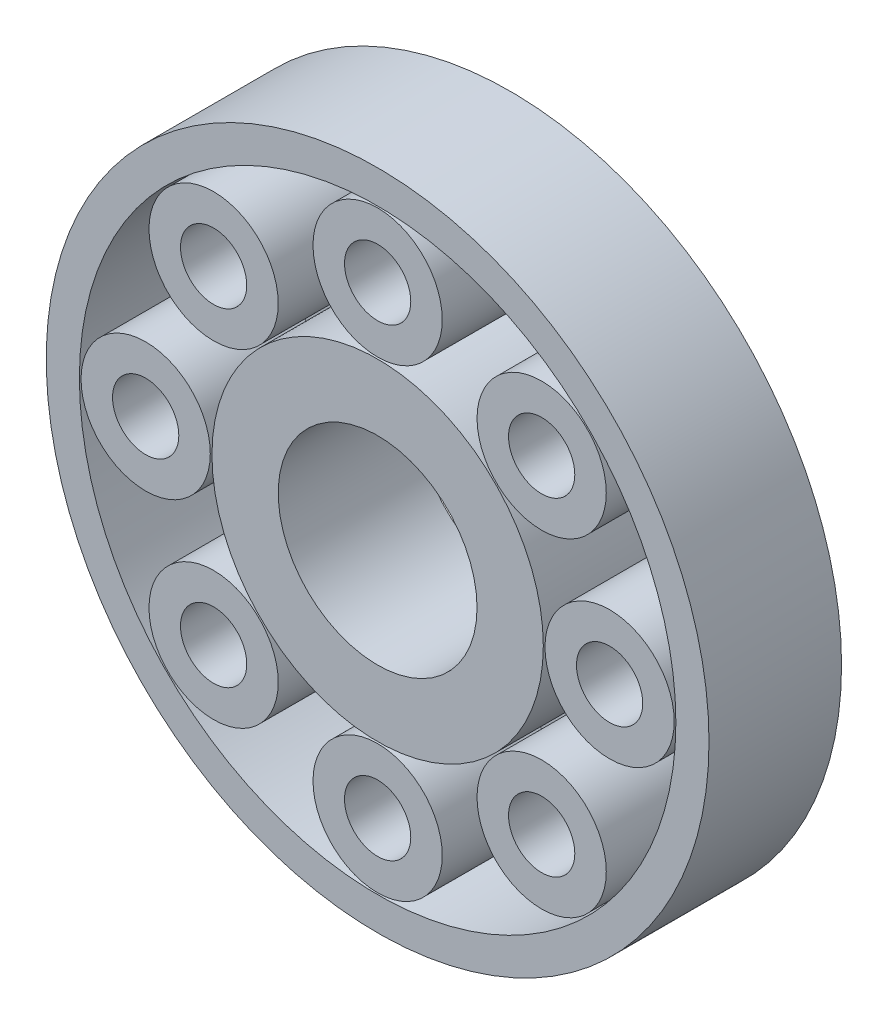
SolidWorks part; units mm, degrees
ref_plane "Front Plane" through (0, 0, 0) normal (0, 0, 1) x (1, 0, 0)
ref_plane "Top Plane" through (0, 0, 0) normal (0, 1, 0) x (1, 0, 0)
ref_plane "Right Plane" through (0, 0, 0) normal (1, 0, 0) x (0, 0, -1)
sketch "Sketch1" plane through (0, 0, 0) normal (0, 0, 1) x (1, 0, 0)
  circle A0 centre (0, 0) radius 10
  dimension "D1" = 20
extrude "Boss-Extrude1" add sketch "Sketch1" along normal blind 4
sketch "Sketch5" plane through (0, 0, 0) normal (0, 0, -1) x (-1, 0, 0)
  circle A0 centre (0, 0) radius 9
  circle A1 centre (0, 0) radius 10 construction
  circle A2 centre (0, 7) radius 1.95
  circle A3 centre (0, 0) radius 5
  circle A4 centre (4.9497, 4.9497) radius 1.95
  circle A5 centre (7, 0) radius 1.95
  circle A6 centre (4.9497, -4.9497) radius 1.95
  circle A7 centre (0, -7) radius 1.95
  circle A8 centre (-4.9497, -4.9497) radius 1.95
  circle A9 centre (-7, 0) radius 1.95
  circle A10 centre (-4.9497, 4.9497) radius 1.95
  point P24 (0, 0)
  dimension "D1" = 1
  dimension "D2" = 3.9
  dimension "D4" = 10
  dimension "D3" = 7
extrude "Cut-Extrude5" cut sketch "Sketch5" against normal up to surface (4 mm away) from offset 0.5 contours A7 A0 A6 A3 | A8 A0 A7 A3 | A9 A0 A8 A3 | A10 A0 A9 A3 | A10 A3 A2 A0 | A4 A0 A2 A3 | A5 A0 A4 A3 | A6 A0 A5 A3 region at (8.9745, 0, 0) up to face at (10, 0, 4) offset against normal yes
sketch "Sketch10" plane through (0, 0, 0) normal (0, 0, -1) x (-1, 0, 0)
  circle A0 centre (0, 0) radius 4
  dimension "D1" = 8
extrude "Boss-Extrude12" add sketch "Sketch10" along normal blind 0.2
sketch "Sketch8" plane through (0, 0, 4) normal (0, 0, 1) x (1, 0, 0)
  circle A0 centre (0, 0) radius 3
  circle A1 centre (0, 7) radius 1
  circle A3 centre (4.9497, 4.9497) radius 1
  circle A4 centre (7, 0) radius 1
  circle A5 centre (4.9497, -4.9497) radius 1
  circle A6 centre (0, -7) radius 1
  circle A7 centre (-4.9497, -4.9497) radius 1
  circle A8 centre (-7, 0) radius 1
  circle A9 centre (-4.9497, 4.9497) radius 1
  circle A10 centre (0, 0) radius 4 construction
  point P24 (0, 0)
  dimension "D1" = 2
  dimension "D2" = 1
extrude "Cut-Extrude7" cut sketch "Sketch8" against normal up to next
fillet "Fillet2" radius 0.1 1 edges at (-4, 0, -0.2)
